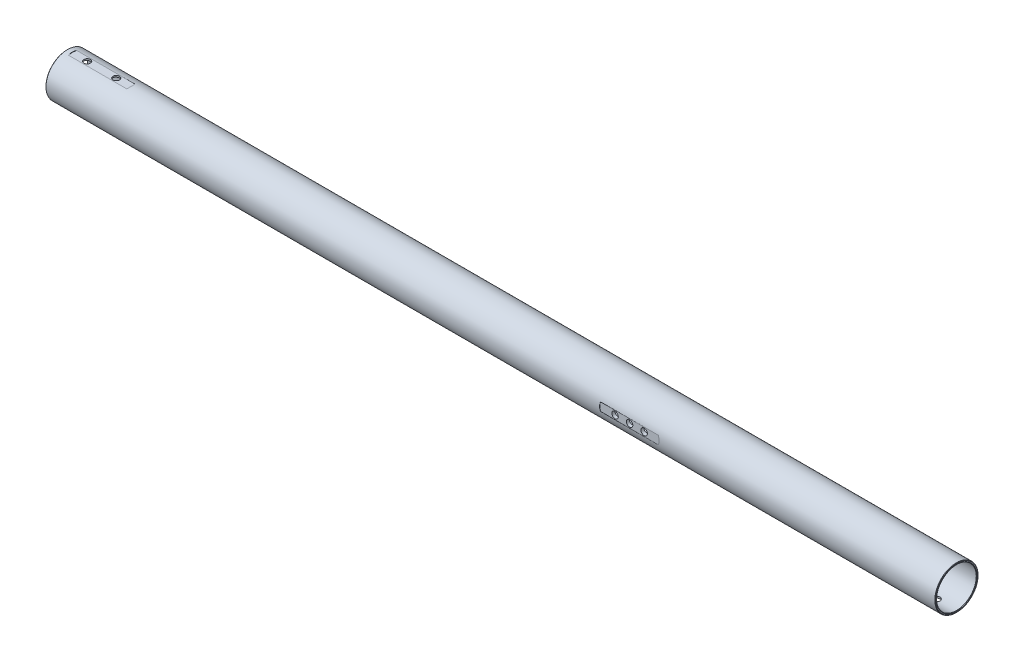
SolidWorks part; units mm, degrees
material "Stainless Steel (ferritic)"
ref_plane "Front Plane" through (0, 0, 0) normal (0, 0, 1) x (1, 0, 0)
ref_plane "Top Plane" through (0, 0, 0) normal (0, 1, 0) x (1, 0, 0)
ref_plane "Right Plane" through (0, 0, 0) normal (1, 0, 0) x (0, 0, -1)
sketch "Sketch1" plane through (0, 0, 0) normal (1, 0, 0) x (0, 0, -1)
  circle A0 centre (0, 0) radius 25
  dimension "D1" = 50
extrude "Extrude-Thin1" add sketch "Sketch1" along normal mid plane 1030 thin thin type one direction reverse wall 2
extrude "Extrude-Thin2" add sketch "Sketch1<3>" against normal blind 90 from offset 210 thin thin type one direction reverse wall 4
sketch "Sketch1<3>" plane through (0, 0, 0) normal (1, 0, 0) x (0, 0, -1) same geometry as "Sketch1"
sketch "Sketch3" plane through (0, 0, 0) normal (0, 1, 0) x (1, 0, 0)
  line L0 (-491.7775, 0) -> (-458.1225, 0) construction
  line L1 (-491.7775, 17.4725) -> (-458.1225, 17.4725)
  line L2 (-491.7775, -17.4725) -> (-458.1225, -17.4725)
  line L4 (-515, 25) -> (-515, -25) construction
  line L5 (0, -27.5) -> (0, 27.5) construction
  line L6 (491.7775, 0) -> (458.1225, 0) construction
  line L7 (491.7775, 17.4725) -> (458.1225, 17.4725)
  line L8 (491.7775, -17.4725) -> (458.1225, -17.4725)
  arc A1 (-491.7775, 17.4725) -> (-491.7775, -17.4725) centre (-491.7775, 0) ccw
  arc A2 (-458.1225, -17.4725) -> (-458.1225, 17.4725) centre (-458.1225, 0) ccw
  arc A3 (491.7775, 17.4725) -> (491.7775, -17.4725) centre (491.7775, 0) cw
  arc A4 (458.1225, -17.4725) -> (458.1225, 17.4725) centre (458.1225, 0) cw
  point P3 (-474.95, 0)
  point P14 (474.95, 0)
  dimension "D2" = 5.75
  dimension "D1" = 68.6
  dimension "D3" = 33.655
extrude "Cut-Extrude1" cut sketch "Sketch3" along normal through all from offset 24.54 contours L2 A2 L1 A1 region at (-474.95, 0, 0)
sketch "Sketch8" plane through (0, 0, 0) normal (0, 0, 1) x (1, 0, 0)
  line L0 (-272.5275, 0) -> (-238.8725, 0) construction
  line L1 (-272.5275, 17.4725) -> (-238.8725, 17.4725)
  line L2 (-272.5275, -17.4725) -> (-238.8725, -17.4725)
  line L4 (-515, 25) -> (-515, -25) construction
  line L5 (143.8725, 0) -> (177.5275, 0) construction
  line L6 (143.8725, 17.4725) -> (177.5275, 17.4725)
  line L7 (143.8725, -17.4725) -> (177.5275, -17.4725)
  line L13 (515, -25) -> (515, 25) construction
  arc A1 (-272.5275, 17.4725) -> (-272.5275, -17.4725) centre (-272.5275, 0) ccw
  arc A2 (-238.8725, -17.4725) -> (-238.8725, 17.4725) centre (-238.8725, 0) ccw
  arc A3 (143.8725, 17.4725) -> (143.8725, -17.4725) centre (143.8725, 0) ccw
  arc A4 (177.5275, -17.4725) -> (177.5275, 17.4725) centre (177.5275, 0) ccw
  point P3 (-255.7, 0)
  point P13 (160.7, 0)
  dimension "D2" = 225
  dimension "D1" = 68.6
  dimension "D3" = 33.655
  dimension "D6" = 320
  dimension "D4" = 68.6
  dimension "D5" = 33.655
extrude "Cut-Extrude2" cut sketch "Sketch8" against normal through all from offset 24.54 contours L2 A2 L1 A1 region at (-255.7, 0, 0) offset against normal yes
extrude "Cut-Extrude3" cut sketch "Sketch3<3>" against normal through all from offset 24.54 contours A4 L8 A3 L7 region at (474.95, 0, 0) offset against normal yes
sketch "Sketch3<3>" plane through (0, 0, 0) normal (0, 1, 0) x (1, 0, 0) same geometry as "Sketch3"
extrude "Cut-Extrude4" cut sketch "Sketch8<4>" along normal through all from offset 24.54 contours L7 A4 L6 A3 region at (160.7, 0, 0)
sketch "Sketch8<4>" plane through (0, 0, 0) normal (0, 0, 1) x (1, 0, 0) same geometry as "Sketch8"
hole_wizard "M (0.295) Diameter Hole3" positions "Sketch11" profile "Sketch12" hole size "M" standard "ANSI Inch" end condition up to next
sketch "Sketch11" plane through (0, 24.54, 0) normal (0, 1, 0) x (1, 0, 0)
  point P0 (-491.7775, 0)
  point P3 (-458.1225, 0)
sketch "Sketch12" plane through (-491.7775, 24.54, 0) normal (1, 0, 0) x (0, 0, 1)
  line L0 (0, 0) -> (0, 1.54)
  line L1 (0, 1.54) -> (3.7465, 1.54)
  line L2 (3.7465, 1.54) -> (3.7465, 0)
  line L5 (3.7465, 0) -> (0, 0)
  line L11 (0, -6.35) -> (0, 107.95) construction
  dimension "Thru Hole Dia." = 7.493
  dimension "Thru Hole Depth" = 1.54
hole_wizard "M (0.295) Diameter Hole4" positions "Sketch13" profile "Sketch14" hole size "M" standard "ANSI Inch" end condition up to next
sketch "Sketch13" plane through (0, 0, -24.54) normal (0, 0, -1) x (-1, 0, 0)
  point P0 (238.8725, 0)
  point P3 (272.5275, 0)
sketch "Sketch14" plane through (-238.8725, 0, -24.54) normal (1, 0, 0) x (0, 1, 0)
  line L0 (0, 0) -> (0, 1.54)
  line L1 (0, 1.54) -> (3.7465, 1.54)
  line L2 (3.7465, 1.54) -> (3.7465, 0)
  line L5 (3.7465, 0) -> (0, 0)
  line L11 (0, -6.35) -> (0, 107.95) construction
  dimension "Thru Hole Dia." = 7.493
  dimension "Thru Hole Depth" = 1.54
hole_wizard "M (0.295) Diameter Hole5" positions "Sketch15" profile "Sketch16" hole size "M" standard "ANSI Inch" end condition up to next
sketch "Sketch15" plane through (0, 0, 24.54) normal (0, 0, 1) x (1, 0, 0)
  point P0 (143.8725, 0)
  point P3 (160.7, 0)
  point P6 (177.5275, 0)
sketch "Sketch16" plane through (143.8725, 0, 24.54) normal (1, 0, 0) x (0, -1, 0)
  line L0 (0, 0) -> (0, 3.54)
  line L1 (0, 3.54) -> (3.7465, 3.54)
  line L2 (3.7465, 3.54) -> (3.7465, 0)
  line L5 (3.7465, 0) -> (0, 0)
  line L11 (0, -6.35) -> (0, 107.95) construction
  dimension "Thru Hole Dia." = 7.493
  dimension "Thru Hole Depth" = 3.54
hole_wizard "M (0.295) Diameter Hole6" positions "Sketch18" profile "Sketch19" hole size "M" standard "ANSI Inch" end condition up to next
sketch "Sketch18" plane through (0, -24.54, 0) normal (0, -1, 0) x (-1, 0, 0)
  point P0 (-491.7775, 0)
  point P3 (-458.1225, 0)
sketch "Sketch19" plane through (491.7775, -24.54, 0) normal (1, 0, 0) x (0, 0, -1)
  line L0 (0, 0) -> (0, 1.54)
  line L1 (0, 1.54) -> (3.7465, 1.54)
  line L2 (3.7465, 1.54) -> (3.7465, 0)
  line L5 (3.7465, 0) -> (0, 0)
  line L11 (0, -6.35) -> (0, 107.95) construction
  dimension "Thru Hole Dia." = 7.493
  dimension "Thru Hole Depth" = 1.54
chamfer "Chamfer1" distance 0.5 angle 45 4 edges at (-515, 0, -23) (-515, 0, -25) (515, 0, -23) (515, 0, -25)
